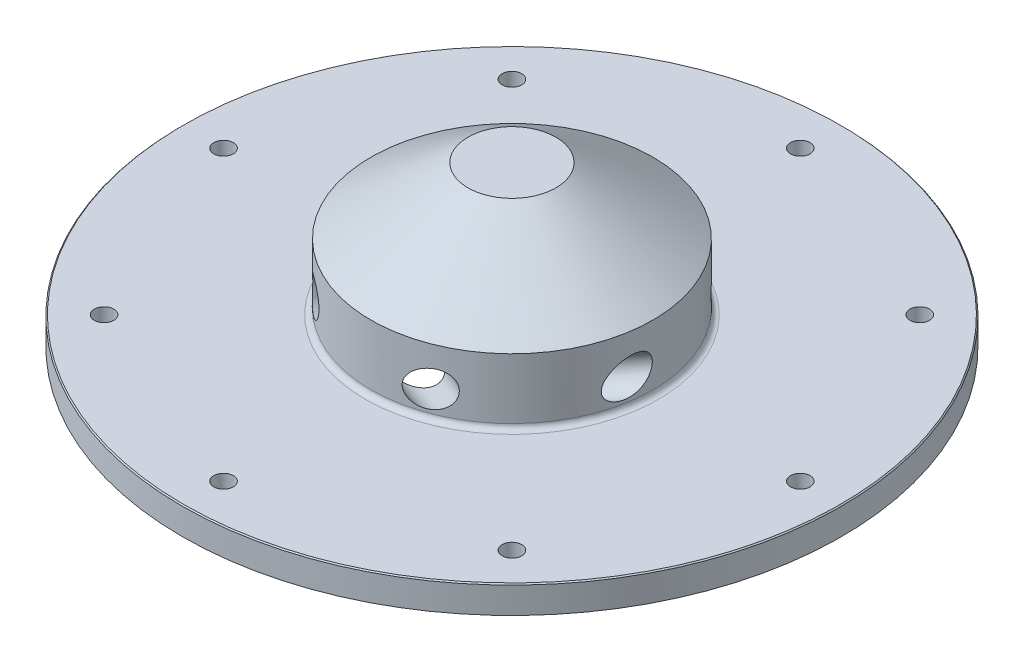
SolidWorks part; units mm, degrees
material "7075-T6 (SN)"
ref_plane "Front Plane" through (0, 0, 0) normal (0, 0, 1) x (1, 0, 0)
ref_plane "Top Plane" through (0, 0, 0) normal (0, 1, 0) x (1, 0, 0)
ref_plane "Right Plane" through (0, 0, 0) normal (1, 0, 0) x (0, 0, -1)
sketch "Sketch2" plane through (0, 0, 0) normal (0, 1, 0) x (1, 0, 0)
  circle A0 centre (0, 0) radius 38.1
  dimension "D1" = 76.2
extrude "Boss-Extrude1" add sketch "Sketch2" along normal blind 3.175
hole_wizard "Tap Drill for #4-40 Tap1" positions "Sketch3" profile "Sketch4" hole size "#4-40" standard "ANSI Inch" end condition through all
sketch "Sketch3" plane through (0, 0, 0) normal (0, -1, 0) x (-1, 0, 0)
  point P0 (0, -33.3375)
  dimension "D1" = 33.3375
sketch "Sketch4" plane through (0, 0, 33.3375) normal (1, 0, 0) x (0, 0, -1)
  line L0 (0, 0) -> (0, 3.175)
  line L1 (0, 3.175) -> (1.1303, 3.175)
  line L2 (1.1303, 3.175) -> (1.1303, 0)
  line L5 (1.1303, 0) -> (0, 0)
  line L11 (0, -6.35) -> (0, 107.95) construction
  dimension "Thru Hole Dia." = 2.2606
  dimension "Thru Hole Depth" = 3.175
pattern_circular "CirPattern1" count 8 over 360 about axis through (0, 0, 0) along (0, 1, 0) of "Tap Drill for #4-40 Tap1"
sketch "Sketch5" plane through (0, 3.175, 0) normal (0, 1, 0) x (1, 0, 0)
  circle A0 centre (0, 0) radius 28.575
  dimension "D1" = 57.15
sketch "Sketch7" plane through (0, 3.175, 0) normal (0, 1, 0) x (1, 0, 0)
  circle A0 centre (0, 0) radius 16.31
  dimension "D1" = 32.62
extrude "Boss-Extrude2" add sketch "Sketch7" along normal blind 7.62
sketch "Sketch8" plane through (0, 0, 0) normal (0, -1, 0) x (1, 0, 0)
  circle A0 centre (0, 0) radius 12.5
  dimension "D1" = 25
extrude "Cut-Extrude1" cut sketch "Sketch8" against normal blind 8.89
sketch "Sketch13" plane through (0, 10.795, 0) normal (0, 1, 0) x (1, 0, 0)
  circle A0 centre (0, 0) radius 16.31
  circle A1 centre (0, 0) radius 16.31 construction
  dimension "D1" = 0
ref_plane "Plane2" through (0, 18.415, 0) normal (0, 1, 0) x (1, 0, 0)
sketch "Sketch14" plane through (0, 18.415, 0) normal (0, 1, 0) x (1, 0, 0)
  circle A0 centre (0, 0) radius 5.08
  dimension "D1" = 10.16
loft "Loft2" add profiles "Sketch14", "Sketch13" connector at (-0.0647, 18.415, 5.0796) connector at (0, 10.795, 16.31)
fillet "Fillet1" radius 0.635 1 edges at (0, 8.89, -12.5)
chamfer "Chamfer1" distance 0.127 angle 45 1 edges at (0, 3.175, 38.1)
ref_plane "Plane4" through (0, 7.62, 0) normal (0, 1, 0) x (1, 0, 0)
fillet "Fillet2" radius 0.635 1 edges at (0, 3.175, 16.31)
ref_axis "Axis1" through (41.91, 7.62, 0) along (-1, 0, 0)
ref_plane "Plane3" through (0, 0.5104, 1.905) normal (0, 0.2588, 0.9659) x (-1, 0, 0)
sketch "Sketch16" plane through (0, 0.5104, 1.905) normal (0, 0.2588, 0.9659) x (-1, 0, 0)
  circle A0 centre (10.212, -2.7899) radius 1.9844
  dimension "D1" = 3.9688
  dimension "D2" = 10.212
  dimension "D3" = 2.7899
extrude "Cut-Extrude2" cut sketch "Sketch16" along normal through all
pattern_circular "CirPattern2" count 6 over 360 about axis through (0, 10.795, 0) along (0, 1, 0) of "Cut-Extrude2"
